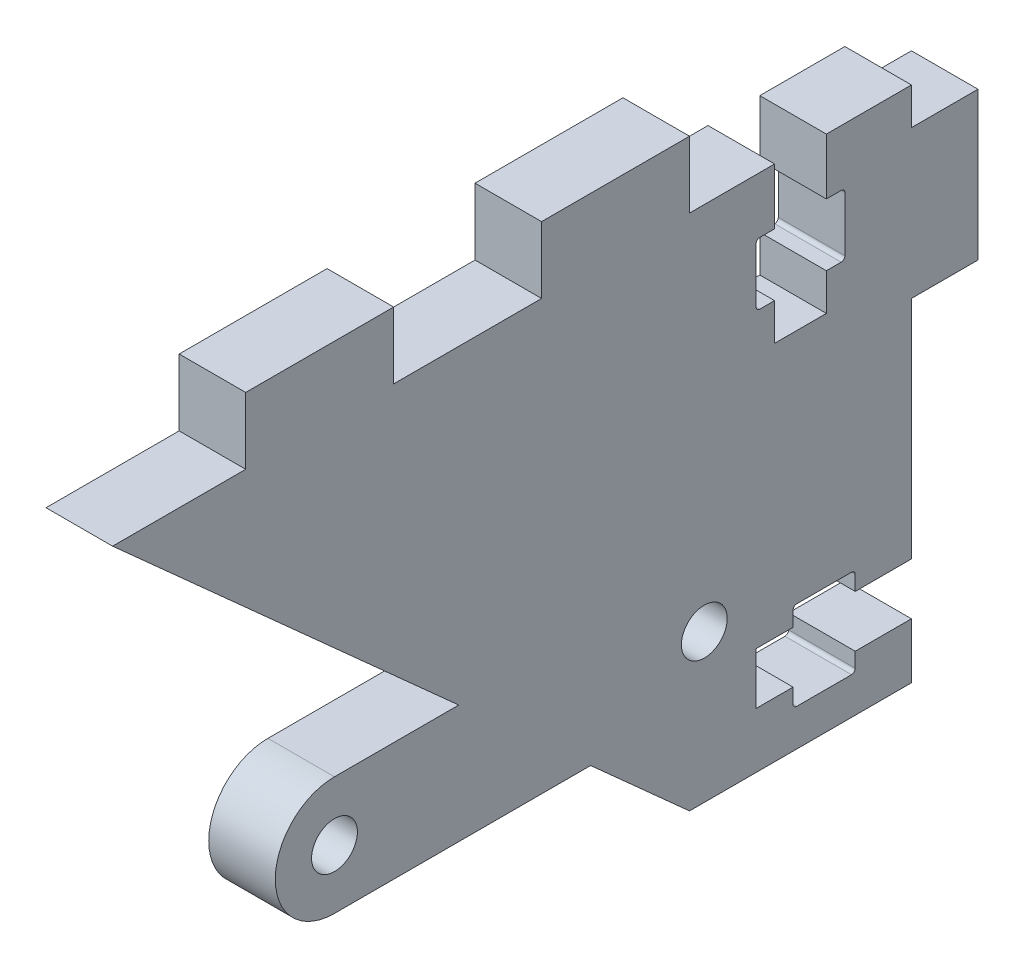
SolidWorks part; units mm, degrees
ref_plane "Front Plane" through (0, 0, 0) normal (0, 0, 1) x (1, 0, 0)
ref_plane "Top Plane" through (0, 0, 0) normal (0, 1, 0) x (1, 0, 0)
ref_plane "Right Plane" through (0, 0, 0) normal (1, 0, 0) x (0, 0, -1)
sketch "Sketch1" plane through (0, 0, 0) normal (1, 0, 0) x (0, 0, -1)
  line L0 (0, 0) -> (0, -35)
  line L1 (0, -35) -> (-54, 0)
  line L2 (-54, 0) -> (0, 0)
  dimension "D1" = 35
  dimension "D2" = 54
extrude "Boss-Extrude1" add sketch "Sketch1" along normal blind 4.5
sketch "Sketch2" plane through (4.5, 0, 0) normal (1, 0, 0) x (0, 0, -1)
  line L0 (0, -35) -> (0, 0) construction
  line L1 (-4.5, -2.5) -> (4.5, -2.5)
  line L2 (-4.5, -2.5) -> (-4.5, -12.5)
  line L3 (-4.5, -12.5) -> (4.5, -12.5)
  line L4 (4.5, -2.5) -> (4.5, -12.5)
  line L5 (-4.5, -2.5) -> (4.5, -12.5) construction
  line L6 (-4.5, -12.5) -> (4.5, -2.5) construction
  line L7 (0, 0) -> (-54, 0) construction
  point P0 (0, -7.5)
  dimension "D1" = 10
  dimension "D2" = 7.5
  dimension "D3" = 4.5
extrude "Boss-Extrude2" add sketch "Sketch2" against normal through all
sketch "Sketch3" plane through (4.5, 0, 0) normal (1, 0, 0) x (0, 0, -1)
  line L0 (0, -35) -> (-15, -35)
  line L1 (0, -25) -> (-54, 0)
  line L4 (0, -35) -> (0, -12.5) construction
  line L5 (0, -25) -> (0, -35)
  line L6 (-54, 0) -> (-15, -35)
  dimension "D1" = 15
  dimension "D2" = 10
extrude "Boss-Extrude3" add sketch "Sketch3" against normal through all
sketch "Sketch4" plane through (4.5, 0, 0) normal (1, 0, 0) x (0, 0, -1)
  line L0 (0, -29.5) -> (-10.5, -29.5) construction
  line L1 (0, -35) -> (0, -12.5) construction
  line L2 (0, -27.75) -> (-10.5, -27.75) construction
  line L3 (-10.5, -27.75) -> (-10.5, -31.25) construction
  line L4 (0, -31.25) -> (0, -27.75)
  line L5 (0, -27.75) -> (-3.8, -27.75)
  line L6 (-3.8, -27.75) -> (-3.8, -26.75)
  line L7 (-4.05, -26.5) -> (-7.75, -26.5)
  line L8 (-8, -26.75) -> (-8, -27.75)
  line L9 (-8, -27.75) -> (-10.5, -27.75)
  line L10 (-10.5, -27.75) -> (-10.5, -31.25)
  line L12 (0, -31.25) -> (-10.5, -31.25) construction
  line L13 (-8, -31.25) -> (-10.5, -31.25)
  line L14 (-8, -32.25) -> (-8, -31.25)
  line L15 (-4.05, -32.5) -> (-7.75, -32.5)
  line L16 (-3.8, -31.25) -> (-3.8, -32.25)
  line L17 (0, -31.25) -> (-3.8, -31.25)
  line L18 (4.5, -12.5) -> (4.5, -2.5) construction
  line L19 (0, -18.5) -> (-33.3857, -18.5) construction
  line L20 (-54, 0) -> (-15, -35) construction
  line L37 (0, -31.25) -> (-10.5, -31.25) construction
  arc A0 (-8, -32.25) -> (-7.75, -32.5) centre (-7.75, -32.25) ccw
  arc A1 (-4.05, -32.5) -> (-3.8, -32.25) centre (-4.05, -32.25) ccw
  arc A2 (-3.8, -26.75) -> (-4.05, -26.5) centre (-4.05, -26.75) ccw
  arc A3 (-7.75, -26.5) -> (-8, -26.75) centre (-7.75, -26.75) ccw
  point P10 (4.5, -7.5)
  point P20 (-8, -32.5)
  point P23 (-3.8, -32.5)
  point P26 (-3.8, -26.5)
  point P29 (-8, -26.5)
  dimension "D7" = 0.25
  dimension "D1" = 10.5
  dimension "D2" = 1.75
  dimension "D3" = 3
  dimension "D4" = 4.2
  dimension "D5" = 8
  dimension "D6" = 22
extrude "Cut-Extrude1" cut sketch "Sketch4" against normal through all
sketch "Sketch5" plane through (4.5, 0, 0) normal (1, 0, 0) x (0, 0, -1)
  line L0 (0, 0) -> (-54, 0) construction
  line L1 (-25, 4.5) -> (-15, 4.5)
  line L2 (-25, 4.5) -> (-25, 0)
  line L3 (0, 0) -> (-54, 0) construction
  line L4 (-15, 4.5) -> (-15, 0)
  line L5 (-25, 4.5) -> (-20, 0) construction
  line L6 (-20, 0) -> (-15, 4.5) construction
  line L7 (-30, 0) -> (-30, 4.5) construction
  line L8 (-40, 0) -> (-45, 4.5) construction
  line L9 (-35, 4.5) -> (-40, 0) construction
  line L10 (-45, 4.5) -> (-45, 0)
  line L12 (-35, 4.5) -> (-35, 0)
  line L13 (-35, 4.5) -> (-45, 4.5)
  line L14 (-20, 0) -> (-15, 4.5) construction
  line L15 (-15, 0) -> (-25, 0)
  line L16 (-35, 0) -> (-45, 0)
  point P0 (-20, 0)
  point P14 (-40, 0)
  dimension "D3" = 4.5
  dimension "D1" = 20
  dimension "D2" = 10
  dimension "D4" = 20
  dimension "D5" = 5
extrude "Boss-Extrude4" add sketch "Sketch5" against normal through all
sketch "Sketch8" [suppressed] plane through (4.5, 0, 0) normal (1, 0, 0) x (0, 0, -1)
  line L0 (-15, -30) -> (-27, -30) construction
  line L1 (-15, -35) -> (-27, -35)
  line L2 (-15, -25) -> (-27, -25)
  line L3 (-15, -35) -> (0, -35) construction
  line L4 (-15, -25) -> (-15, -35)
  arc A1 (-27, -25) -> (-27, -35) centre (-27, -30) ccw
  dimension "D5" = 5
  dimension "D1" = 0
  dimension "D2" = 12
  dimension "D3" = 0
  dimension "D4" = 10
extrude "Boss-Extrude5" [suppressed] add sketch "Sketch8" against normal up to surface (4.5 mm away) up to face at (0, -17.3125, 11.7125)
sketch "Sketch9" [suppressed] plane through (4.5, 0, 0) normal (1, 0, 0) x (0, 0, -1)
  line L0 (-27, -30) -> (-22, -30) construction
  line L1 (-27, -27) -> (-22, -27)
  line L2 (-27, -33) -> (-22, -33)
  arc A0 (-27, -27) -> (-27, -33) centre (-27, -30) ccw
  arc A1 (-22, -33) -> (-22, -27) centre (-22, -30) ccw
  point P3 (-24.5, -30)
  dimension "D1" = 3
  dimension "D2" = 5
extrude "Cut-Extrude3" [suppressed] cut sketch "Sketch9" against normal through all
sketch "Sketch10" plane through (0, 0, 0) normal (-1, 0, 0) x (0, 0, 1)
  line L0 (15, -35) -> (54, -12)
  line L1 (54, -12) -> (54, 0)
  line L3 (54, 0) -> (15, -35)
  dimension "D1" = 12
extrude "Boss-Extrude6" [suppressed] add sketch "Sketch10" against normal through all
sketch "Sketch6" plane through (4.5, 0, 0) normal (1, 0, 0) x (0, 0, -1)
  line L0 (-30, 0) -> (-30, -10.5) construction
  line L1 (-25, 0) -> (-35, 0) construction
  line L2 (-28.25, -10.5) -> (-31.75, -10.5) construction
  line L3 (-31.75, -10.5) -> (-31.75, 0) construction
  line L4 (-28.25, 0) -> (-31.75, 0)
  line L5 (-31.75, 0) -> (-31.75, -3.8)
  line L6 (-31.75, -3.8) -> (-32.75, -3.8)
  line L7 (-33, -4.05) -> (-33, -7.75)
  line L8 (-32.75, -8) -> (-31.75, -8)
  line L9 (-31.75, -8) -> (-31.75, -10.5)
  line L10 (-31.75, -10.5) -> (-28.25, -10.5)
  line L11 (-28.25, -10.5) -> (-28.25, 0) construction
  line L12 (-28.25, -8) -> (-28.25, -10.5)
  line L13 (-27.25, -8) -> (-28.25, -8)
  line L14 (-27, -4.05) -> (-27, -7.75)
  line L15 (-28.25, -3.8) -> (-27.25, -3.8)
  line L16 (-28.25, 0) -> (-28.25, -3.8)
  arc A0 (-33, -7.75) -> (-32.75, -8) centre (-32.75, -7.75) ccw
  arc A1 (-32.75, -3.8) -> (-33, -4.05) centre (-32.75, -4.05) ccw
  arc A2 (-27.25, -3.8) -> (-27, -4.05) centre (-27.25, -4.05) cw
  arc A3 (-27, -7.75) -> (-27.25, -8) centre (-27.25, -7.75) cw
  point P12 (-33, -8)
  point P15 (-33, -3.8)
  point P26 (-27, -3.8)
  point P27 (-27, -8)
  dimension "D1" = 10.5
  dimension "D2" = 1.75
  dimension "D4" = 4.2
  dimension "D6" = 0.25
  dimension "D3" = 8
  dimension "D5" = 3
extrude "Cut-Extrude2" [suppressed] cut sketch "Sketch6" against normal through all
sketch "Sketch11" plane through (0, 0, 0) normal (-1, 0, 0) x (0, 0, 1)
  line L0 (7.5, 0) -> (7.5, -10.5) construction
  line L1 (0, 0) -> (15, 0) construction
  line L2 (5.75, -10.5) -> (9.25, -10.5)
  line L3 (9.25, -10.5) -> (9.25, -8)
  line L4 (9.25, -8) -> (10.25, -8)
  line L5 (10.5, -7.75) -> (10.5, -4.05)
  line L6 (10.25, -3.8) -> (9.25, -3.8)
  line L7 (9.25, -3.8) -> (9.25, 0)
  line L8 (9.25, 0) -> (5.75, 0)
  line L9 (9.25, -8) -> (9.25, -3.8) construction
  line L10 (0, 0) -> (15, 0) construction
  line L11 (5.75, -8) -> (5.75, -3.8) construction
  line L12 (5.75, -3.8) -> (5.75, 0)
  line L13 (4.75, -3.8) -> (5.75, -3.8)
  line L14 (4.5, -7.75) -> (4.5, -4.05)
  line L15 (5.75, -8) -> (4.75, -8)
  line L16 (5.75, -10.5) -> (5.75, -8)
  arc A0 (10.5, -4.05) -> (10.25, -3.8) centre (10.25, -4.05) ccw
  arc A1 (4.75, -3.8) -> (4.5, -4.05) centre (4.75, -4.05) ccw
  arc A2 (10.25, -8) -> (10.5, -7.75) centre (10.25, -7.75) ccw
  arc A3 (4.5, -7.75) -> (4.75, -8) centre (4.75, -7.75) ccw
  point P11 (7.5, 0)
  point P22 (10.5, -3.8)
  point P25 (4.5, -3.8)
  point P28 (10.5, -8)
  point P31 (4.5, -8)
  dimension "D7" = 0.25
  dimension "D1" = 10.5
  dimension "D3" = 3
  dimension "D8" = 0.25
  dimension "D2" = 4.2
  dimension "D4" = 8
  dimension "D5" = 1.75
  dimension "D6" = 0
extrude "Cut-Extrude4" cut sketch "Sketch11" against normal through all
sketch "Sketch12" plane through (0, 0, 0) normal (-1, 0, 0) x (0, 0, 1)
  line L0 (28, -16) -> (16, -4) construction
  line L1 (28, -16) -> (28, -2.75) construction
  line L2 (28, -16) -> (40, -4) construction
  line L3 (28, -16) -> (14.75, -16) construction
  line L4 (28, -16) -> (16, -28) construction
  line L5 (28, -16) -> (16, -4) construction
  line L6 (0, -27.75) -> (0, -12.5) construction
  line L7 (25, 0) -> (35, 0) construction
  circle A0 centre (28, -16) radius 13.25
  circle A1 centre (16, -4) radius 1.55
  circle A2 centre (40, -4) radius 1.55
  circle A3 centre (16, -28) radius 1.55
  dimension "D1" = 26.5
  dimension "D2" = 3.1
  dimension "D3" = 12
  dimension "D4" = 45
  dimension "D5" = 28
  dimension "D6" = 16
extrude "Cut-Extrude5" [suppressed] cut sketch "Sketch12" against normal through all
sketch "Sketch13" [suppressed] plane through (0, 0, 0) normal (-1, 0, 0) x (0, 0, 1)
  line L0 (39.2845, -9.0557) -> (43.5428, -6.4352)
  line L1 (20.5179, -26.9353) -> (17.6945, -31.0619)
  line L6 (28, -16) -> (54, 0) construction
  line L7 (28, -16) -> (15, -35) construction
  arc A0 (20.5179, -26.9353) -> (39.2845, -9.0557) centre (28, -16) ccw
  arc A1 (17.6945, -31.0619) -> (43.5428, -6.4352) centre (28, -16) ccw
  arc A3 (40.6311, -11.9977) -> (22.6595, -28.1261) centre (28, -16) ccw construction
  dimension "D1" = 5
extrude "Boss-Extrude7" [suppressed] add sketch "Sketch13" against normal through all
sketch "Sketch14" [suppressed] plane through (0, 0, 0) normal (-1, 0, 0) x (0, 0, 1)
  line L0 (28, -2.75) -> (28, -29.25) construction
  line L1 (28, -16) -> (40, -28) construction
  circle A0 centre (28, -16) radius 13.25 construction
  circle A1 centre (40, -28) radius 3.5
  dimension "D2" = 7
  dimension "D1" = 45
  dimension "D3" = 12
extrude "Boss-Extrude8" [suppressed] add sketch "Sketch14" against normal through all
sketch "Sketch15" [suppressed] plane through (0, 0, 0) normal (-1, 0, 0) x (0, 0, 1)
  line L0 (42.4749, -30.4749) -> (28, -16) construction
  arc A0 (38.305, -31.0622) -> (43.0622, -26.305) centre (40, -28) ccw construction
  circle A1 centre (40, -28) radius 1.55
  dimension "D1" = 3.1
extrude "Cut-Extrude6" [suppressed] cut sketch "Sketch15" against normal through all
sketch "Sketch16" plane through (4.5, 0, 0) normal (1, 0, 0) x (0, 0, -1)
  line L0 (0, -25) -> (-39, -25) construction
  line L1 (0, -27.75) -> (0, -12.5) construction
  line L2 (-20, -25) -> (-39, -25) construction
  line L3 (-20, -29) -> (-39, -29)
  line L4 (-20, -21) -> (-39, -21)
  line L5 (-15, -35) -> (0, -35) construction
  arc A0 (-20, -29) -> (-20, -21) centre (-20, -25) ccw
  arc A1 (-39, -21) -> (-39, -29) centre (-39, -25) ccw
  point P5 (-29.5, -25)
  point P12 (0, -20.125)
  dimension "D1" = 4
  dimension "D2" = 10
  dimension "D3" = 39
  dimension "D4" = 20
extrude "Boss-Extrude9" add sketch "Sketch16" against normal through all
sketch "Sketch17" plane through (4.5, 0, 0) normal (1, 0, 0) x (0, 0, -1)
  line L0 (-43, -25) -> (0, -25) construction
  line L1 (0, -27.75) -> (0, -12.5) construction
  line L2 (-26.5, -25) -> (-26.5, -20.0064) construction
  arc A0 (-39, -21) -> (-39, -29) centre (-39, -25) ccw construction
  circle A1 centre (-39, -25) radius 1.55
  circle A2 centre (-14, -25) radius 1.55
  dimension "D1" = 3.1
  dimension "D2" = 12.5
extrude "Cut-Extrude7" cut sketch "Sketch17" against normal through all
equation "\"X-ROD-SPACING\"=45"
equation "\"Y-ROD-SPACING\"=75"
equation "\"Z-ROD-SPACING\"=17.5"
equation "\"Y-BED-OFFSET\"=2"
equation "\"Y-BED-ROD-INSET\"=3.5"
equation "\"Y-BED-SCREW-SPACING\"=209"
equation "\"Y-BED-SCREW-CUTOUT-SLOT-HEIGHT\"=2"
equation "\"T-SLOT-NUT-FILLET-RADIUS\"=0.25"
equation "\"T-SLOT-SCREW-SHAFT-RADIUS\"=1.75"
equation "\"T-SLOT-SCREW-SHAFT-CUTOUT-LENGTH\"=10.5"
equation "\"T-SLOT-NUT-DEPTH\"=4.2"
equation "\"T-SLOT-NUT-WIDTH\"=3"
equation "\"T-SLOT-NUT-END-DISTANCE\"=8"
equation "\"ACRYLIC-THICKNESS\"=10"
equation "\"ACRYLIC-THICKNESS2\"=4.5"
equation "\"ACRYLIC-TAB-CUTOUT-SIZE\"=\"ACRYLIC-THICKNESS\"+\"ACRYLIC-TAB-TOLERANCE\"*2"
equation "\"ACRYLIC-TAB-WIDTH\"=\"ACRYLIC-THICKNESS\""
equation "\"ACRYLIC-M3-HOLE\"=3.1"
equation "\"SMOOTHROD-CAP-SCREW-DISTANCE\"=20"
equation "\"FRAME-WIDTH-INNER\"=370"
equation "\"NEMA17-HOLE-SPACING\"=31"
equation "\"NEMA17-CENTRAL-CUTOUT\"=22.5"
equation "\"Z-BRACKET-REACH\"=55"
equation "\"Z-ROD-INSET\"=16"
equation "\"TOP-BRACKET-SPACING\"=40"
equation "\"SMOOTHROD-X-LENGTH\"=350"
equation "\"SMOOTHROD-Y-LENGTH\"=350"
equation "\"SMOOTHROD-Z-LENGTH\"=350"
equation "\"SMOOTHROD-TIGHTENING-HEADROOM\"=.25"
equation "\"LEADSCREW-Z-LENGTH\"=300"
equation "\"SCREW-LENGTH-FRAME\"=\"ACRYLIC-THICKNESS\" + 10"
equation "\"SCREW-LENGTH-MOTOR\"=\"ACRYLIC-THICKNESS\" + 5"
equation "\"SCREW-LENGTH-EXTRUDER\"=28"
equation "\"SCREW-HEAD-RADIUS\"=6"
equation "\"PRINTED-X-SMOOTHROD-DIAMETER\"=8.2"
equation "\"PRINTED-X-SMOOTHROD-CUTOUT\"=10"
equation "\"PRINTED-X-BASE-HEIGHT\"=10"
equation "\"PRINTED-LM8UU-CUTOUT-SIZE\"=15.25"
equation "\"PRINTED-LM8UU-CUTOUT-LENGTH\"=24.5"
equation "\"PRINTED-X-IDLER-HEIGHT\"=16"
equation "\"PSU-MOUNTING-WIDTH\"=95"
equation "\"PSU-MOUNTING-HEIGHT\"=177"
equation "\"Y-BELT-TO-ROD-DISTANCE\"=20"
equation "\"SPOOL-HOLDER-ROD-SPACING\"=150"
equation "\"ACRYLIC-X-CARRIAGE-WIDTH\"=55"
equation "\"ACRYLIC-X-CARRIAGE-HEIGHT\"=75"
equation "\"ACRYLIC-X-CARRIAGE-SCREW-SPACING-X\"=15"
equation "\"ACRYLIC-X-CARRIAGE-SCREW-SPACING-Y\"=33"
equation "\"ACRYLIC-X-CARRIAGE-CENTER-TAB-SPACING\"=14"
equation "\"ACRYLIC-X-CARRIAGE-EXTRUDER-SHELF-DEPTH\"=\"ACRYLIC-X-CARRIAGE-EXTRUDER-OFFSET\" + 28"
equation "\"D2@Sketch1\"=\"ACRYLIC-X-CARRIAGE-EXTRUDER-SHELF-DEPTH\""
equation "\"D1@Boss-Extrude1\"=\"ACRYLIC-THICKNESS2\""
equation "\"D1@Sketch2\"=\"ACRYLIC-TAB-WIDTH\""
equation "\"D3@Sketch2\"=\"ACRYLIC-THICKNESS2\""
equation "\"ACRYLIC-X-CARRIAGE-LM8UU-CUTOUT-WIDTH\"=24.25"
equation "\"ACRYLIC-X-CARRIAGE-EXTRUDER-BRACE-SPACING\"=23"
equation "\"ACRYLIC-X-CARRIAGE-EXTRUDER-BRACE-HEIGHT\"=35"
equation "\"D1@Sketch1\"=\"ACRYLIC-X-CARRIAGE-EXTRUDER-BRACE-HEIGHT\""
equation "\"D1@Sketch4\"=\"T-SLOT-SCREW-SHAFT-CUTOUT-LENGTH\""
equation "\"D2@Sketch4\"=\"T-SLOT-SCREW-SHAFT-RADIUS\""
equation "\"D3@Sketch4\"=\"T-SLOT-NUT-WIDTH\""
equation "\"D4@Sketch4\"=\"T-SLOT-NUT-DEPTH\""
equation "\"D5@Sketch4\"=\"T-SLOT-NUT-END-DISTANCE\""
equation "\"D7@Sketch4\"=\"T-SLOT-NUT-FILLET-RADIUS\""
equation "\"ACRYLIC-X-CARRIAGE-EXTRUDER-BRACE-SCREW-SPACING\"=22"
equation "\"D6@Sketch4\"=\"ACRYLIC-X-CARRIAGE-EXTRUDER-BRACE-SCREW-SPACING\""
equation "\"ACRYLIC-X-CARRIAGE-EXTRUDER-BRACE-TAB-OFFSET\"=20"
equation "\"D1@Sketch5\"=\"ACRYLIC-X-CARRIAGE-EXTRUDER-BRACE-TAB-OFFSET\""
equation "\"D2@Sketch5\"=\"ACRYLIC-TAB-WIDTH\""
equation "\"D3@Sketch5\"=\"ACRYLIC-THICKNESS2\""
equation "\"ACRYLIC-X-CARRIAGE-EXTRUDER-OFFSET\"=26"
equation "\"ACRYLIC-X-CARRIAGE-EXTRUDER-ANGLE\"=90"
equation "\"D1@Sketch6\"=\"T-SLOT-SCREW-SHAFT-CUTOUT-LENGTH\""
equation "\"D2@Sketch6\"=\"T-SLOT-SCREW-SHAFT-RADIUS\""
equation "\"D3@Sketch6\"=\"T-SLOT-NUT-END-DISTANCE\""
equation "\"D4@Sketch6\"=\"T-SLOT-NUT-DEPTH\""
equation "\"D5@Sketch6\"=\"T-SLOT-NUT-WIDTH\""
equation "\"D6@Sketch6\"=\"T-SLOT-NUT-FILLET-RADIUS\""
equation "\"D1@Sketch11\"=\"T-SLOT-SCREW-SHAFT-CUTOUT-LENGTH\""
equation "\"D2@Sketch11\"=\"T-SLOT-NUT-DEPTH\""
equation "\"D3@Sketch11\"=\"T-SLOT-NUT-WIDTH\""
equation "\"D4@Sketch11\"=\"T-SLOT-NUT-END-DISTANCE\""
equation "\"D5@Sketch11\"=\"T-SLOT-SCREW-SHAFT-RADIUS\""
equation "\"D7@Sketch11\"=\"T-SLOT-NUT-FILLET-RADIUS\""
equation "\"D8@Sketch11\"=\"T-SLOT-NUT-FILLET-RADIUS\""
equation "\"D2@Sketch12\"=\"ACRYLIC-M3-HOLE\""
equation "\"D1@Sketch15\"=\"ACRYLIC-M3-HOLE\""
equation "\"D1@Sketch17\"=\"ACRYLIC-M3-HOLE\""
